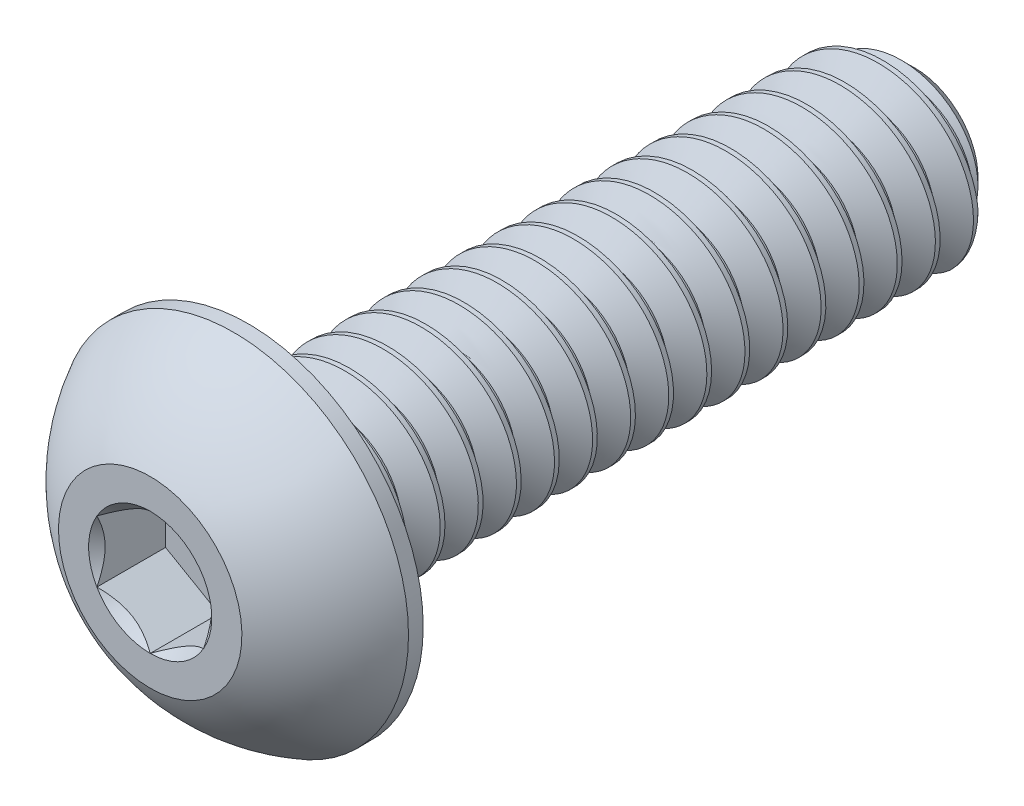
SolidWorks part; units mm, degrees
material "AISI 316 Annealed Stainless Steel Bar (SS)"
ref_plane "Front" through (0, 0, 0) normal (0, 0, 1) x (1, 0, 0)
ref_plane "Top" through (0, 0, 0) normal (0, 1, 0) x (1, 0, 0)
ref_plane "Right" through (0, 0, 0) normal (1, 0, 0) x (0, 0, -1)
sketch "Sketch1" plane through (0, 0, 0) normal (1, 0, 0) x (0, 0, -1)
  line L2 (1.1684, 1.0922) -> (9.1059, 1.0922)
  line L3 (9.1059, 1.0922) -> (9.1059, 0)
  line L4 (9.1059, 0) -> (1.1684, 0)
  line L6 (0.9931, 2.0828) -> (1.1684, 2.0828) construction
  line L7 (9.1059, 1.0922) -> (9.1059, -1.0922) construction
  line L8 (0, 0) -> (1.1684, 0) construction
  line L9 (1.1684, 2.0828) -> (1.1684, -2.0828) construction
  line L11 (1.1684, 1.0922) -> (1.1684, 0)
  line L13 (0, 0.635) -> (0, -0.635) construction
  line L14 (0, 0.635) -> (0, 1.0922) construction
  arc A3 (0, 1.0922) -> (0.9931, 2.0828) centre (2.08, 0) cw construction
  dimension "D1" = 0.1753
revolve "Revolve1" add sketch "Sketch1" angle 360 mid plane about L4
sketch "Sketch3" plane through (0, 0, -9.1059) normal (0, 0, -1) x (-1, 0, 0)
  circle A0 centre (0, 0) radius 1.0922
curve "Helix/Spiral1" pitch 0.4536 height 9.1059 radius 1.0922 centre (0, 0, -9.1059) axis (0, 0, 1) start towards (0, 1, 0)
sketch "Sketch2" plane through (0, 0, 0) normal (1, 0, 0) x (0, 0, -1)
  line L0 (9.1059, 1.0922) -> (9.5028, 1.0922)
  line L1 (9.5028, 1.0922) -> (9.3327, 0.7976)
  line L2 (9.3327, 0.7976) -> (9.276, 0.7976)
  line L3 (9.276, 0.7976) -> (9.1059, 1.0922)
  line L4 (9.1909, 0.9449) -> (9.4177, 0.9449) construction
  dimension "D1" = 60
  dimension "D2" = 0.0567
  dimension "D3" = 0.2268
chamfer "Chamfer1" distance 0.3402 angle 45 1 edges at (0, 1.0922, -9.1059)
sweep "Cut-Sweep1" cut profiles "Sketch2" path "Helix/Spiral1"
sketch "Sketch7" plane through (0, 0, 0) normal (1, 0, 0) x (0, 0, -1)
  line L6 (0.9931, 2.0828) -> (1.1684, 2.0828) construction
  line L8 (0, 0) -> (1.1684, 0) construction
  line L11 (1.1684, 2.0828) -> (1.1684, -2.0828) construction
  line L12 (0.9931, 2.0828) -> (1.1684, 2.0828)
  line L13 (0, 0) -> (1.1684, 0)
  line L14 (0, 0.635) -> (0, -0.635) construction
  line L15 (1.1684, 2.0828) -> (1.1684, 0)
  line L16 (0, 1.0922) -> (0, 0)
  arc A2 (0.9931, 2.0828) -> (0, 1.0922) centre (2.08, 0) ccw construction
  arc A3 (0.9931, 2.0828) -> (0, 1.0922) centre (2.08, 0) ccw
revolve "Revolve2" add sketch "Sketch7" angle 360 mid plane about L13
sketch "Sketch5" plane through (0, 0, 0) normal (0, 0, 1) x (1, 0, 0)
  line L1 (0.635, -0.3666) -> (0.635, 0.3666)
  line L2 (0.635, 0.3666) -> (0, 0.7332)
  line L3 (0, 0.7332) -> (-0.635, 0.3666)
  line L4 (-0.635, 0.3666) -> (-0.635, -0.3666)
  line L5 (-0.635, -0.3666) -> (0, -0.7332)
  line L6 (0, -0.7332) -> (0.635, -0.3666)
  circle A0 centre (0, 0) radius 0.635 construction
extrude "Cut-Extrude2" cut sketch "Sketch5" against normal blind 0.8179
sketch "Sketch6" plane through (0, 0, 0) normal (0, 0, 1) x (1, 0, 0)
  circle A0 centre (0, 0) radius 0.7332
extrude "Cut-Extrude3" cut sketch "Sketch6" against normal blind 0.8179 draft 45
sketch "Sketch9" [suppressed] plane through (0, 0, -8.2296) normal (0, 0, 1) x (1, 0, 0)
  circle A2 centre (0, 0) radius 7.9375
extrude "Boss-Extrude2" [suppressed] add sketch "Sketch9" against normal offset from surface (25.4 mm away) 22.225 up to face at (0, 0.752, -9.1059)
sketch "Sketch10" plane through (0, 0, 0) normal (1, 0, 0) x (0, 0, -1)
  line L0 (9.1059, 1.0922) -> (9.1059, -1.0922) construction
  point P0 (8.4255, -1.0922)
  dimension "D1" = 0.6804
equation "\"D3@Helix/Spiral1\" = \"Lg@Sketch1\" + \"Head Ht@Sketch1\""
equation "\"D2@Sketch2\" = \"D4@Helix/Spiral1\" * .125"
equation "\"D3@Sketch2\" = \"D4@Helix/Spiral1\" * .5"
equation "\"D1@Chamfer1\" = \"D4@Helix/Spiral1\" * .75"
equation "\"D1@Cut-Extrude2\" = \"Head Ht@Sketch1\" * .7"
equation "\"D1@Sketch1\" = \"Head Ht@Sketch1\" * .15"
equation "\"D1@Sketch10\" = \"D4@Helix/Spiral1\" * 1.5"
equation "\"D1@Cut-Extrude3\" = \"D1@Cut-Extrude2\""
